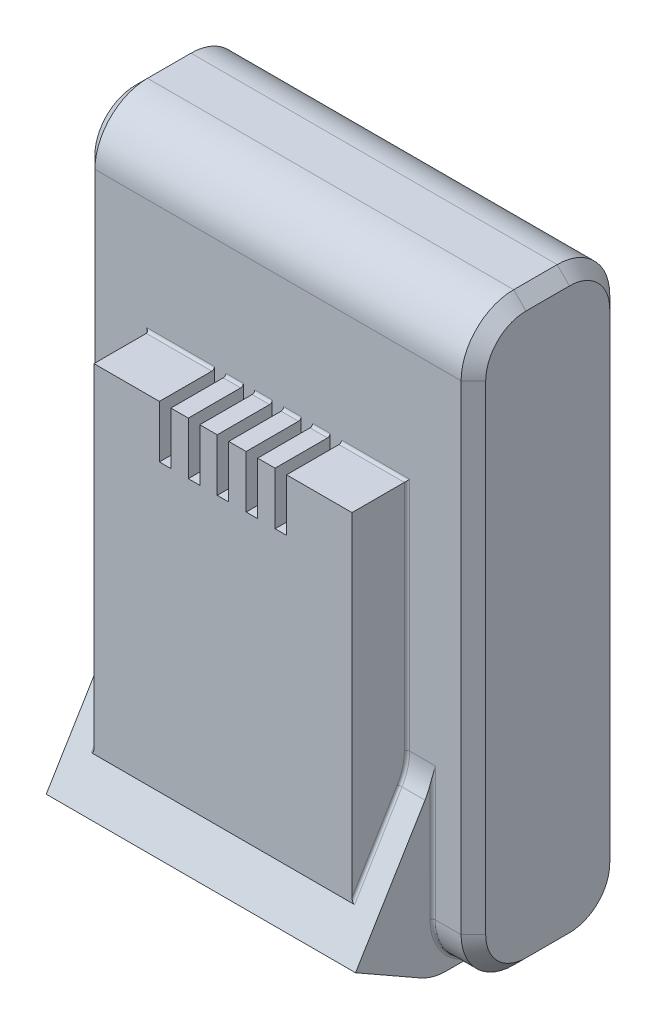
SolidWorks part; units mm, degrees
ref_plane "Front Plane" through (0, 0, 0) normal (0, 0, 1) x (1, 0, 0)
ref_plane "Top Plane" through (0, 0, 0) normal (0, 1, 0) x (1, 0, 0)
ref_plane "Right Plane" through (0, 0, 0) normal (1, 0, 0) x (0, 0, -1)
sketch "Sketch1" plane through (0, 0, 0) normal (0, 0, 1) x (1, 0, 0)
  line L1 (-37.7571, -56.5023) -> (37.7571, -56.5023)
  line L2 (-37.7571, -56.5023) -> (-37.7571, 56.5023)
  line L3 (-37.7571, 56.5023) -> (37.7571, 56.5023)
  line L4 (37.7571, -56.5023) -> (37.7571, 56.5023)
  line L5 (-37.7571, -56.5023) -> (37.7571, 56.5023) construction
  line L6 (-37.7571, 56.5023) -> (37.7571, -56.5023) construction
  point P0 (0, 0)
  dimension "D1" = 75.5142
  dimension "D2" = 113.0046
extrude "Boss-Extrude1" add sketch "Sketch1" along normal blind 28.7274
fillet "Fillet1" radius 10.16 4 edges at (0, -56.5023, 0) (0, -56.5023, 28.7274) (0, 56.5023, 28.7274) (0, 56.5023, 0)
sketch "Sketch2" plane through (0, 0, 28.7274) normal (0, 0, 1) x (1, 0, 0)
  line L0 (37.7571, -56.5023) -> (-37.7571, -56.5023) construction
  line L1 (-24.9301, -56.5023) -> (24.9301, -56.5023)
  line L2 (-24.9301, -56.5023) -> (-24.9301, 24.373)
  line L3 (-24.9301, 24.373) -> (24.9301, 24.373)
  line L4 (24.9301, -56.5023) -> (24.9301, 24.373)
  point P6 (0, 24.373)
  dimension "D1" = 49.8602
extrude "Boss-Extrude2" add sketch "Sketch2" along normal blind 10.6299 and the other way up to vertex (10.16 mm away) other way up to point (37.7571, -56.5023, 18.5674)
ref_plane "Plane1" through (29.8831, 0, 0) normal (1, 0, 0) x (0, 0, -1)
ref_plane "Plane2" through (-29.8831, 0, 0) normal (1, 0, 0) x (0, 0, -1)
sketch "Sketch3" plane through (29.8831, 0, 0) normal (1, 0, 0) x (0, 0, -1)
  line L0 (-28.7274, -56.5023) -> (-28.7274, -23.4315)
  line L2 (-28.7274, 24.373) -> (-28.7274, -46.3423) construction
  line L3 (-28.7274, -56.5023) -> (-43.6231, -48.0239)
  line L4 (-43.6231, -48.0239) -> (-28.7274, -23.4315)
  line L5 (-39.3573, -56.5023) -> (-39.3573, 24.373) construction
  line L6 (-28.7274, -23.4315) -> (-18.5674, -23.4315)
  line L7 (-28.7274, -23.4315) -> (-28.7274, -56.5023)
  line L8 (-28.7274, -56.5023) -> (-18.5674, -56.5023)
  line L9 (-18.5674, -23.4315) -> (-18.5674, -56.5023)
  point P3 (-39.3573, -40.9812)
  dimension "D1" = 33.0708
  dimension "D2" = 65.3542
extrude "Boss-Extrude3" add sketch "Sketch3" against normal up to surface (59.7662 mm away) contours L9 L6 L0 L8 | L4 L0 L3 region at (29.8831, -39.9669, 23.6474) up to plane "Plane2"
sketch "Sketch4" plane through (29.8831, 0, 0) normal (1, 0, 0) x (0, 0, -1)
  line L0 (-43.6231, -48.0239) -> (-28.7274, -56.5023)
  line L1 (-43.6231, -48.0239) -> (-54.4343, -67.0183)
  line L2 (-28.7274, -56.5023) -> (-39.5386, -75.4967)
  line L3 (-54.4343, -67.0183) -> (-39.5386, -75.4967)
extrude "Cut-Extrude1" cut sketch "Sketch4" against normal through all
chamfer "Chamfer1" distance 2.38 angle 45 16 edges at (-37.7571, 0, 0) (-37.7571, 53.5265, 2.9758) (-37.7571, -53.5265, 2.9758) (-37.7571, 56.5023, 14.3637) (-37.7571, -56.5023, 14.3637) (-37.7571, 53.5265, 25.7516) (-37.7571, -53.5265, 25.7516) (-37.7571, 0, 28.7274) (37.7571, 53.5265, 2.9758) (37.7571, 56.5023, 14.3637) (37.7571, 0, 0) (37.7571, 53.5265, 25.7516) (37.7571, -53.5265, 2.9758) (37.7571, 0, 28.7274) (37.7571, -56.5023, 14.3637) (37.7571, -53.5265, 25.7516)
fillet "Fillet2" radius 10.16 3 edges at (-27.4066, -23.4315, 28.7274) (27.4066, -23.4315, 28.7274) (0, -56.5023, 28.7274)
fillet "Fillet3" radius 0.508 11 edges at (-29.8831, -53.5265, 25.7516) (-24.9301, -33.4197, 34.7773) (-24.9301, -23.327, 29.1017) (24.9301, -33.4197, 34.7773) (24.9301, -23.327, 29.1017) (29.8831, -53.5265, 25.7516) (-29.8831, -33.4684, 28.7274) (-24.9301, 1.8893, 28.7274) (0, 24.373, 28.7274) (24.9301, 1.8893, 28.7274) (29.8831, -33.4684, 28.7274)
sketch "Sketch5" plane through (0, 0, 39.3573) normal (0, 0, 1) x (1, 0, 0)
  line L1 (-12.3698, 25.6684) -> (12.3698, 25.6684) construction
  line L2 (-12.3698, 25.6684) -> (-12.3698, 14.2384) construction
  line L3 (-12.3698, 14.2384) -> (12.3698, 14.2384) construction
  line L4 (12.3698, 25.6684) -> (12.3698, 14.2384) construction
  line L5 (4.4768, 25.6684) -> (4.4768, 14.2384)
  line L6 (-1.1112, 25.6684) -> (1.1112, 25.6684)
  line L7 (-1.1112, 25.6684) -> (-1.1112, 14.2384)
  line L8 (-1.1112, 14.2384) -> (1.1112, 14.2384)
  line L9 (1.1112, 25.6684) -> (1.1112, 14.2384)
  line L10 (4.4768, 25.6684) -> (6.6993, 25.6684)
  line L11 (6.6993, 25.6684) -> (6.6992, 14.2384)
  line L12 (4.4768, 14.2384) -> (6.6992, 14.2384)
  line L13 (10.0648, 25.6684) -> (10.0648, 14.2384)
  line L14 (10.0648, 25.6684) -> (12.2873, 25.6684)
  line L15 (12.2873, 25.6684) -> (12.2872, 14.2384)
  line L16 (10.0648, 14.2384) -> (12.2872, 14.2384)
  line L17 (-6.6993, 25.6684) -> (-6.6992, 14.2384)
  line L18 (-6.6993, 25.6684) -> (-4.4768, 25.6684)
  line L19 (-4.4768, 25.6684) -> (-4.4768, 14.2384)
  line L20 (-6.6992, 14.2384) -> (-4.4768, 14.2384)
  line L21 (-12.2873, 25.6684) -> (-12.2872, 14.2384)
  line L22 (-12.2873, 25.6684) -> (-10.0648, 25.6684)
  line L23 (-10.0648, 25.6684) -> (-10.0648, 14.2384)
  line L24 (-12.2872, 14.2384) -> (-10.0648, 14.2384)
  point P6 (0, 14.2384)
  point P12 (0, 14.2384)
  dimension "D1" = 24.7396
  dimension "D2" = 11.43
  dimension "D3" = 2.2225
  dimension "D4" = 3
  dimension "D5" = 3
extrude "Cut-Extrude2" cut sketch "Sketch5" against normal up to surface (10.6299 mm away) up to face at (0, -10.4417, 28.7274)
